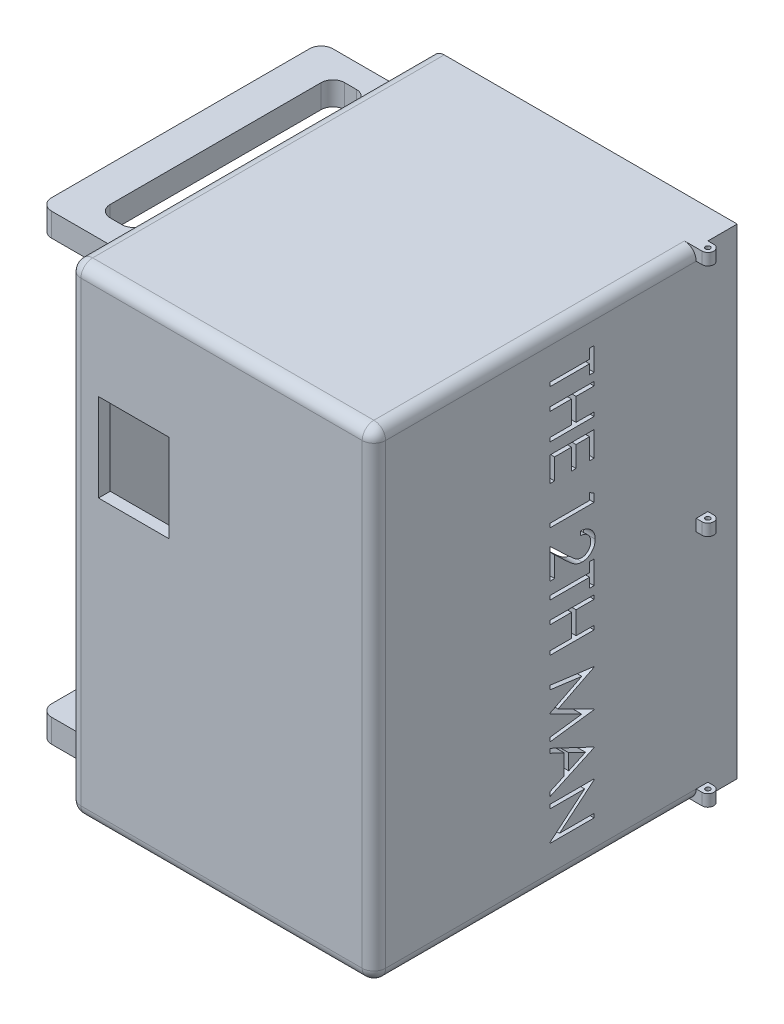
SolidWorks part; units mm, degrees
ref_plane "Front Plane" through (0, 0, 0) normal (0, 0, 1) x (1, 0, 0)
ref_plane "Top Plane" through (0, 0, 0) normal (0, 1, 0) x (1, 0, 0)
ref_plane "Right Plane" through (0, 0, 0) normal (1, 0, 0) x (0, 0, -1)
sketch "Sketch1" plane through (0, 0, 0) normal (0, 0, 1) x (1, 0, 0)
  line L0 (0, 0) -> (66.04, 0)
  line L1 (66.04, 0) -> (66.04, 104.14)
  line L2 (66.04, 104.14) -> (0, 104.14)
  line L3 (0, 104.14) -> (0, 0)
  dimension "D1" = 66.04
  dimension "D2" = 104.14
extrude "Boss-Extrude1" add sketch "Sketch1" along normal blind 78.74
shell "Shell3" thickness 2.54 removed face at (33.02, 52.07, 0)
sketch "Sketch6" plane through (66.04, 0, 0) normal (1, 0, 0) x (0, 0, -1)
  line L0 (-40.5448, 104.14) -> (-40.5448, 0) construction
  line L1 (-78.74, 104.14) -> (0, 104.14) construction
  line L2 (-78.74, 0) -> (0, 0) construction
  text T0 "THE 12TH MAN" font "Century Gothic" height in points 36
extrude "Cut-Extrude7" cut sketch "Sketch6" against normal blind 40.64
sketch "Sketch7" plane through (0, 0, 0) normal (-1, 0, 0) x (0, 0, 1)
  line L0 (39.37, 104.14) -> (39.37, 0) construction
  line L1 (78.74, 104.14) -> (0, 104.14) construction
  line L2 (78.74, 0) -> (0, 0) construction
  text T0 "THE 12TH MAN" font "Century Gothic" height in points 36
extrude "Cut-Extrude9" cut sketch "Sketch7" against normal blind 40.64
sketch "Sketch8" plane through (0, 0, 0) normal (-1, 0, 0) x (0, 0, 1)
  line L0 (0, 52.07) -> (78.74, 52.07) construction
  line L1 (8.89, 7.112) -> (69.85, 7.112)
  line L2 (8.89, 7.112) -> (8.89, 2.032)
  line L3 (8.89, 2.032) -> (69.85, 2.032)
  line L4 (69.85, 7.112) -> (69.85, 2.032)
  line L5 (8.89, 102.108) -> (69.85, 102.108)
  line L6 (8.89, 102.108) -> (8.89, 97.028)
  line L7 (8.89, 97.028) -> (69.85, 97.028)
  line L8 (69.85, 102.108) -> (69.85, 97.028)
  line L9 (0, 104.14) -> (0, 0) construction
  line L10 (78.74, 104.14) -> (78.74, 0) construction
  line L11 (39.37, 104.14) -> (39.37, 0) construction
  line L12 (78.74, 104.14) -> (0, 104.14) construction
  line L13 (78.74, 0) -> (0, 0) construction
  point P20 (39.37, 102.108)
  dimension "D1" = 5.08
  dimension "D2" = 60.96
  dimension "D3" = 2.032
extrude "Boss-Extrude3" add sketch "Sketch8" along normal blind 15.24
sketch "Sketch9" plane through (0, 102.108, 0) normal (0, 1, 0) x (1, 0, 0)
  line L0 (0, -78.74) -> (0, 0) construction
  line L1 (-7.62, -13.97) -> (0, -13.97)
  line L2 (-7.62, -13.97) -> (-7.62, -64.77)
  line L3 (-7.62, -64.77) -> (0, -64.77)
  line L4 (0, -13.97) -> (0, -64.77)
  line L5 (-15.24, -69.85) -> (0, -69.85) construction
  line L6 (-15.24, -69.85) -> (0, -69.85)
  line L7 (-15.24, -39.37) -> (0, -39.37) construction
  line L8 (-15.24, -69.85) -> (-15.24, -8.89) construction
  point P8 (-7.62, -39.37)
  point P9 (-7.62, -69.85)
  line M5 (0, -69.85) -> (0, -8.89)
  dimension "D1" = 50.8
sketch "Sketch11" plane through (0, 0, 0) normal (0, 1, 0) x (1, 0, 0)
  line L1 (66.04, -6.35) -> (67.31, -6.35)
  line L2 (67.31, -8.89) -> (66.04, -8.89)
  line L3 (66.04, -8.89) -> (66.04, -6.35)
  line L4 (66.04, 0) -> (0, 0)
  line L5 (0, 0) -> (0, -78.74)
  line L6 (0, -78.74) -> (66.04, -78.74)
  line L7 (66.04, -78.74) -> (66.04, 0)
  line L8 (66.04, 0) -> (0, 0)
  line L9 (0, 0) -> (0, -78.74)
  line L10 (0, -78.74) -> (66.04, -78.74)
  line L11 (66.04, -78.74) -> (66.04, 0)
  arc A0 (67.31, -6.35) -> (67.31, -8.89) centre (67.31, -7.62) cw
  circle A1 centre (67.31, -7.62) radius 0.508
  dimension "D2" = 1.016
  dimension "D4" = 1.27
  dimension "D3" = 1.27
  dimension "D5" = 6.35
  dimension "D1" = 0
extrude "Boss-Extrude4" add sketch "Sketch11" along normal blind 2.54 contours A0 L1 L3 L2 A1 region at (66.675, 0, 6.3859)
ref_plane "Plane1" through (0, 104.14, 0) normal (0, 1, 0) x (1, 0, 0)
ref_plane "Plane2" through (0, 52.07, 0) normal (0, 1, 0) x (1, 0, 0)
pattern_linear "LPattern1" count 3 spacing 50.8 along (0, 1, 0) of "Boss-Extrude4"
fillet "Fillet1" radius 2.54 8 edges at (0, 52.07, 78.74) (33.02, 104.14, 78.74) (66.04, 52.07, 78.74) (33.02, 0, 78.74) (0, 0, 39.37) (66.04, 0, 43.815) (0, 104.14, 39.37) (66.04, 104.14, 43.815)
extrude "Cut-Extrude10" cut sketch "Sketch9" against normal through all both and the other way through all contours L7 L2 L3 M5 | L2 L7 L4 L1 region at (-3.81, 102.108, 26.67) region at (-3.81, 102.108, 52.07)
fillet "Fillet2" radius 2.54 8 edges at (-7.62, 4.572, 64.77) (-7.62, 4.572, 13.97) (-7.62, 99.568, 64.77) (-7.62, 99.568, 13.97) (0, 4.572, 13.97) (0, 4.572, 64.77) (0, 99.568, 64.77) (0, 99.568, 13.97)
fillet "Fillet3" radius 2.54 4 edges at (-15.24, 4.572, 8.89) (-15.24, 4.572, 69.85) (-15.24, 99.568, 69.85) (-15.24, 99.568, 8.89)
sketch "Sketch12" plane through (0, 0, 0) normal (0, -1, 0) x (1, 0, 0)
  line L0 (2.54, 0) -> (66.04, 0) construction
  line L1 (33.02, 25.4) -> (53.34, 25.4)
  line L2 (33.02, 25.4) -> (33.02, 55.88)
  line L3 (33.02, 55.88) -> (53.34, 55.88)
  line L4 (53.34, 25.4) -> (53.34, 55.88)
  line L5 (66.04, 76.2) -> (66.04, 8.89) construction
  dimension "D1" = 25.4
  dimension "D2" = 12.7
  dimension "D3" = 30.48
  dimension "D4" = 20.32
extrude "Cut-Extrude11" cut sketch "Sketch12" against normal up to surface (2.54 mm away) up to face at (33.02, 2.54, 38.1)
sketch "Sketch13" plane through (0, 0, 78.74) normal (0, 0, 1) x (1, 0, 0)
  line L0 (0, 2.54) -> (0, 101.6) construction
  line L1 (6.35, 62.23) -> (21.59, 62.23)
  line L2 (6.35, 62.23) -> (6.35, 81.28)
  line L3 (6.35, 81.28) -> (21.59, 81.28)
  line L4 (21.59, 62.23) -> (21.59, 81.28)
  line L5 (2.54, 104.14) -> (63.5, 104.14) construction
  dimension "D1" = 6.35
  dimension "D2" = 22.86
  dimension "D3" = 19.05
  dimension "D4" = 15.24
extrude "Cut-Extrude12" cut sketch "Sketch13" against normal up to surface (2.54 mm away) up to face at (33.02, 52.07, 76.2)
